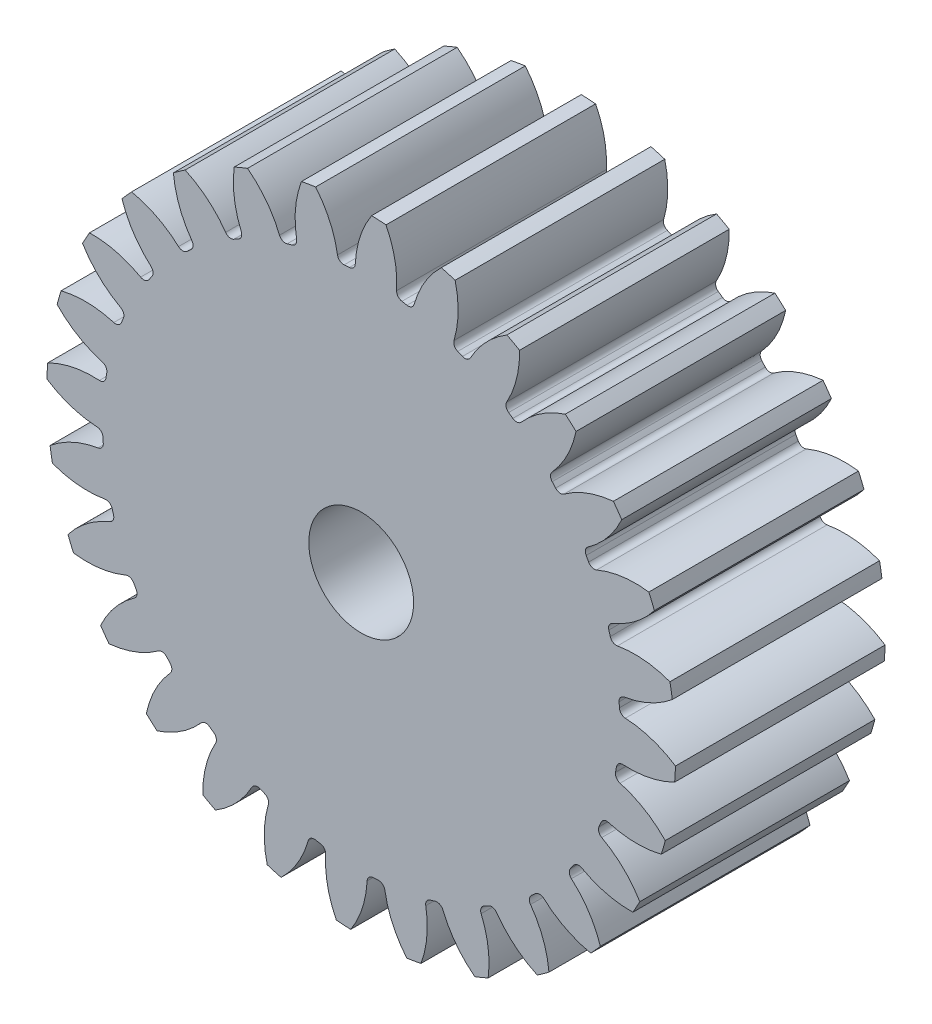
SolidWorks part; units mm, degrees
material "PA Tipo 6"
ref_plane "Front Plane" through (0, 0, 0) normal (0, 0, 1) x (1, 0, 0)
ref_plane "Top Plane" through (0, 0, 0) normal (0, 1, 0) x (1, 0, 0)
ref_plane "Right Plane" through (0, 0, 0) normal (1, 0, 0) x (0, 0, -1)
sketch "Croquis1" plane through (0, 0, 0) normal (0, 0, 1) x (1, 0, 0)
  line L0 (0, 0) -> (0, 111.7136) construction
  line L1 (0, 14) -> (4.4996, 12.3622) construction
  line L2 (0, 0) -> (6.6218, 117.9092) construction
  line L3 (1.5675, 13.912) -> (-3.0871, 12.7883) construction
  circle A0 centre (0, 0) radius 13.1557 construction
  circle A1 centre (0, 0) radius 12.33 construction
  circle A2 centre (0, 0) radius 14 construction
  circle A3 centre (0, 0) radius 15 construction
  arc A4 (0.4978, 14.9917) -> (-0.2887, 12.3266) centre (4.4996, 12.3622) ccw
  arc A5 (1.1839, 14.9532) -> (1.667, 12.2168) centre (-3.0871, 12.7883) cw
  dimension "De" = 30
  dimension "Dp" = 28
  dimension "Dt" = 24.66
  dimension "ct" = 26.3113
  dimension "Ed" = 1.57
sketch "Croquis2" plane through (0, 0, 0) normal (0, 0, 1) x (1, 0, 0)
  circle A0 centre (0, 0) radius 12.33 construction
  circle A1 centre (0, 0) radius 15 construction
  arc A2 (0.4978, 14.9917) -> (-0.2887, 12.3266) centre (4.4996, 12.3622) ccw construction
  arc A3 (1.667, 12.2168) -> (1.1839, 14.9532) centre (-3.0871, 12.7883) ccw construction
  arc A4 (-0.2887, 12.3266) -> (1.667, 12.2168) centre (0, 0) ccw
  arc A5 (1.1839, 14.9532) -> (0.4978, 14.9917) centre (0, 0) ccw
  arc A6 (0.4978, 14.9917) -> (-0.2887, 12.3266) centre (4.4996, 12.3622) ccw
  arc A7 (1.667, 12.2168) -> (1.1839, 14.9532) centre (-3.0871, 12.7883) ccw
extrude "Saliente-Extruir1" add sketch "Croquis2" along normal blind 10
fillet "Redondeo1" radius 0.3 2 edges at (-0.2887, 12.3266, 5) (1.667, 12.2168, 5)
pattern_circular "MatrizC1" count 28 over 360 about axis through (0, 0, 10) along (0, 0, 1) of "Saliente-Extruir1", "Redondeo1"
sketch "Croquis3" plane through (0, 0, 10) normal (0, 0, 1) x (1, 0, 0)
  circle A0 centre (0, 0) radius 2.5
  dimension "D1" = 5
extrude "Cortar-Extruir1" cut sketch "Croquis3" against normal through all
ref_axis "Eje1" through (0, 0, 104.6592) along (0, 0, -1)
equation "\"M\"= 1"
equation "\"N\"= 28"
equation "\"a\"= 20"
equation "\"De@Croquis1\"= \"M\" * ( \"N\" + 2 )"
equation "\"Dp@Croquis1\" = \"M\" * \"N\""
equation "\"Dt@Croquis1\"= \"Dp@Croquis1\" - ( \"M\" * 2 * 1.67 )"
equation "\"ct@Croquis1\"= \"Dp@Croquis1\" * 0.93969"
equation "\"Ed@Croquis1\"= \"M\" * 1.57"
equation "\"r@Redondeo1\"= \"M\" * 0.3"
equation "\"D1@MatrizC1\"=\"N\""
